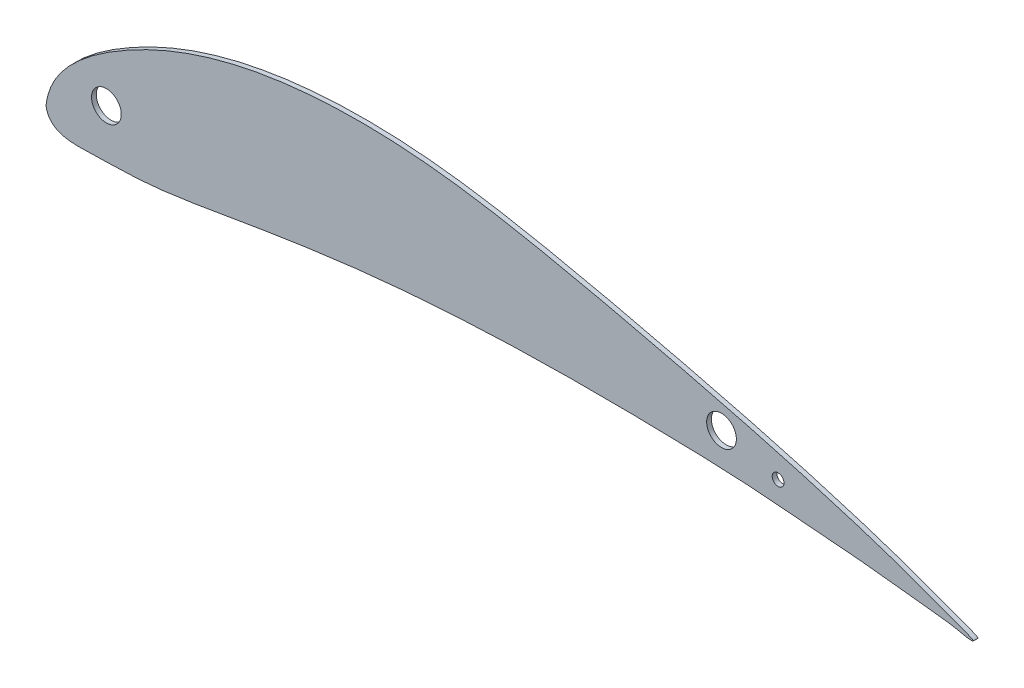
SolidWorks part; units mm, degrees
material "Balsa"
ref_plane "Front Plane" through (0, 0, 0) normal (0, 0, 1) x (1, 0, 0)
ref_plane "Top Plane" through (0, 0, 0) normal (0, 1, 0) x (1, 0, 0)
ref_plane "Right Plane" through (0, 0, 0) normal (1, 0, 0) x (0, 0, -1)
sketch "Sketch1" plane through (0, 0, 0) normal (0, 0, 1) x (1, 0, 0)
  spline S0 degree 3 poles (0.0006, 0.0001) (0.8106, 7.3592) (8.6491, 17.8566) (26.2867, 29.9752) (52.1111, 42.0692) (89.5976, 49.2908) (131.4008, 47.8848) (173.2567, 40.0411) (217.9611, 29.613) (256.9521, 19.5289) (290.3598, 8.711) (301.2732, 4.3828) (314.8169, -0.5162) (309.8463, 0.0001) knots 0 0 0 0 0.060864 0.113688 0.188609 0.312909 0.448482 0.557612 0.691544 0.852438 0.929756 0.976058 1 1 1 1
  spline S1 degree 3 poles (309.8463, 0.0001) (303.9568, 1.471) (293.9895, 2.094) (276.264, 4.5144) (260.8463, 5.4274) (235.8588, 7.8703) (205.1014, 8.8381) (157.7186, 9.0307) (110.4973, 6.1815) (66.5062, -0.5867) (36.4547, -6.0985) (15.3166, -6.1891) (1.2307, -6.9241) (0.0006, 0.0001) knots 0 0 0 0 0.057787 0.095275 0.171021 0.205339 0.335319 0.464904 0.658702 0.785512 0.893517 0.943092 1 1 1 1
extrude "Boss-Extrude1" add sketch "Sketch1" along normal blind 1.5875
sketch "Sketch2" plane through (0, 0, 1.5875) normal (0, 0, 1) x (1, 0, 0)
  line L0 (227.2963, 19.0501) -> (20.32, 10.16) construction
  line L1 (20.32, 10.16) -> (227.2963, 10.16) construction
  line L2 (227.2963, 10.16) -> (227.2963, 19.0501) construction
  circle A0 centre (20.32, 10.16) radius 5
  circle A1 centre (227.2963, 19.0501) radius 5
  circle A2 centre (246.3463, 14.2241) radius 1.9844
  dimension "D2" = 10
  dimension "D3" = 10
  dimension "D6" = 20.32
  dimension "D9" = 3.9688
  dimension "D1" = 82.55
  dimension "D4" = 19.05
  dimension "D5" = 10.16
  dimension "D7" = 63.5
  dimension "D8" = 14.224
extrude "Cut-Extrude1" cut sketch "Sketch2" against normal through all
sketch "Sketch3" plane through (0, 0, 0) normal (0, 0, -1) x (-1, 0, 0)
  line L0 (-309.8463, 0.0001) -> (-259.6129, 0.0001)
